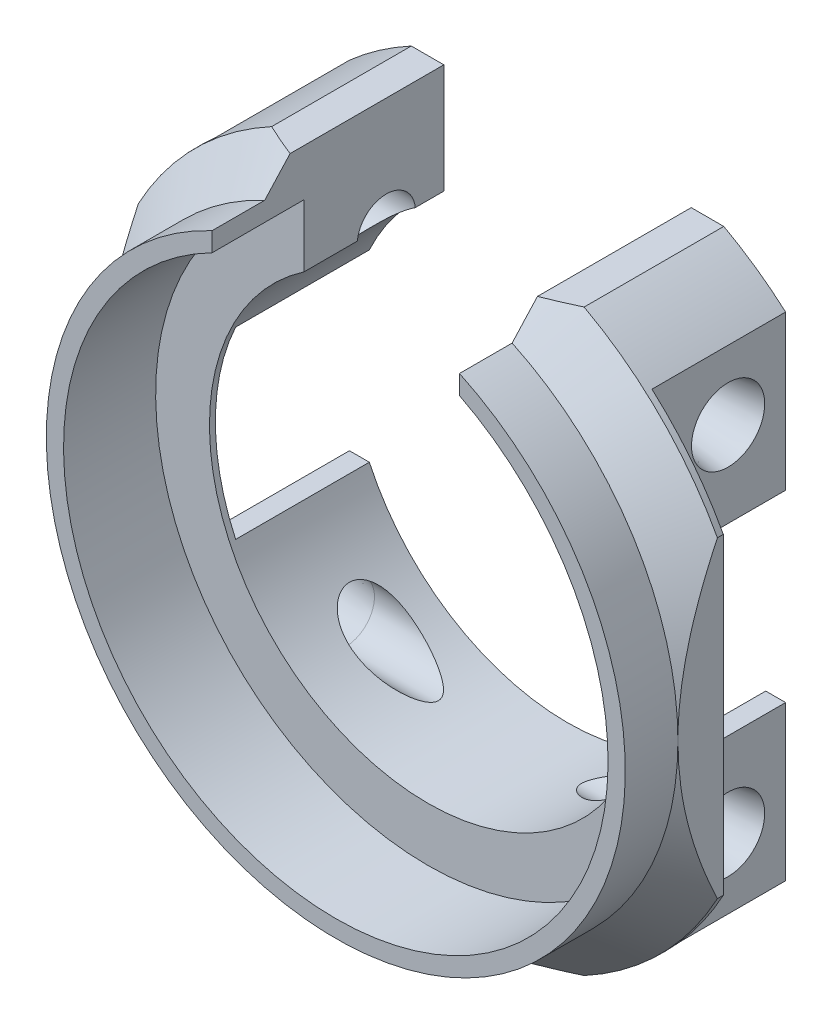
SolidWorks part; units mm, degrees
material "6061-T6 (SS)"
ref_plane "Front Plane" through (0, 0, 0) normal (0, 0, 1) x (1, 0, 0)
ref_plane "Top Plane" through (0, 0, 0) normal (0, 1, 0) x (1, 0, 0)
ref_plane "Right Plane" through (0, 0, 0) normal (1, 0, 0) x (0, 0, -1)
sketch "Sketch1" plane through (0, 0, 0) normal (0, 0, 1) x (1, 0, 0)
  line L1 (-16.637, -17.145) -> (16.637, -17.145) construction
  line L2 (-16.637, -17.145) -> (-16.637, 17.145) construction
  line L3 (-16.637, 17.145) -> (16.637, 17.145) construction
  line L4 (16.637, -17.145) -> (16.637, 17.145) construction
  line L5 (0, 17.145) -> (0, -17.145) construction
  line L6 (-16.637, 0) -> (16.637, 0) construction
  line L7 (-22, -22) -> (22, -22)
  line L8 (-22, -22) -> (-22, 22)
  line L9 (-22, 22) -> (22, 22)
  line L10 (22, -22) -> (22, 22)
  line L11 (0, 22) -> (0, -22) construction
  line L12 (-22, 0) -> (22, 0) construction
  circle A0 centre (0, 0) radius 16.002 construction
  circle A1 centre (0, 0) radius 16.602
  point P0 (0, 0)
  dimension "D3" = 32.004
  dimension "D1" = 33.274
  dimension "D2" = 34.29
  dimension "D4" = 44
  dimension "D6" = 0.6
extrude "Boss-Extrude1" add sketch "Sketch1" along normal blind 0.45
sketch "Sketch2" plane through (0, 0, 0) normal (0, 0, -1) x (-1, 0, 0)
  line L0 (-22, 22) -> (22, 22) construction
  line L1 (-16.5735, -22) -> (16.5735, -22)
  line L2 (-16.5735, -22) -> (-16.5735, 22)
  line L3 (-16.5735, 22) -> (16.5735, 22)
  line L4 (16.5735, -22) -> (16.5735, 22)
  line L5 (0, 22) -> (0, -22) construction
  line L6 (-16.5735, 0) -> (16.5735, 0) construction
  line L7 (15.0611, 6.985) -> (16.5735, 6.985)
  line L9 (15.0611, -6.985) -> (16.5735, -6.985)
  line L11 (-15.0611, -6.985) -> (-16.5735, -6.985)
  line L12 (-15.0611, 6.985) -> (-16.5735, 6.985)
  circle A0 centre (0, 0) radius 16.602 construction
  circle A1 centre (0, 0) radius 16.602
  point P0 (0, 0)
  circle M15 centre (0, 0) radius 16.602
  dimension "D1" = 33.147
  dimension "D2" = 6.985
extrude "Boss-Extrude2" add sketch "Sketch2" along normal blind 10.16 contours L7 L4 L3 M15 | L9 L1 L4 M15 region at (0, -17.0395, 0) region at (0, 17.0395, 0)
sketch "Sketch3" plane through (-16.5735, 0, 0) normal (-1, 0, 0) x (0, 0, 1)
  line L0 (0, 6.985) -> (0, 22) construction
  circle A0 centre (-5.788, 13.4747) radius 2.7813
  circle A1 centre (-5.788, -13.4747) radius 2.7813
  dimension "D3" = 5.5626
  dimension "D1" = 26.9494
  dimension "D2" = 13.4747
  dimension "D4" = 5.788
extrude "Cut-Extrude1" cut sketch "Sketch3" against normal blind 4.064 draft 8
mirror "Mirror1" about plane through (0, 0, 0) normal (1, 0, 0) of "Cut-Extrude1"
sketch "Sketch4" plane through (-12.5095, 0, 0) normal (-1, 0, 0) x (0, 0, 1)
  circle A0 centre (-5.788, -13.4747) radius 2.2101 construction
  circle A1 centre (-5.788, 13.4747) radius 2.2101 construction
  circle A2 centre (-5.788, -13.4747) radius 2.2101
  circle A3 centre (-5.788, 13.4747) radius 2.2101
extrude "Cut-Extrude2" cut sketch "Sketch4" against normal through all
sketch "Sketch5" plane through (0, 0, 0.45) normal (0, 0, 1) x (1, 0, 0)
  circle A0 centre (0, 0) radius 18.4912 construction
  dimension "D1" = 36.9824
sketch "Sketch6" plane through (0, 0, 0.45) normal (0, 0, 1) x (1, 0, 0)
  line L0 (-22, 22) -> (-22, -22) construction
  line L1 (-25, -25) -> (25, -25)
  line L2 (-25, -25) -> (-25, 25)
  line L3 (-25, 25) -> (25, 25)
  line L4 (25, -25) -> (25, 25)
  line L5 (0, 25) -> (0, -25) construction
  line L6 (-25, 0) -> (25, 0) construction
  line L8 (-22, -22) -> (22, -22) construction
  point P0 (0, 0)
  dimension "D1" = 3
  dimension "D2" = 3
chamfer "Chamfer2" distance 2 angle 45 1 edges at (0, -22, -10.16)
sketch "Sketch12" plane through (0, 0, 0.45) normal (0, 0, 1) x (1, 0, 0)
  line L0 (0, 25) -> (0, -25) construction
  circle A0 centre (0, 0) radius 20.291 construction
  circle A1 centre (0, 0) radius 22
  circle A2 centre (0, 0) radius 20.691
  dimension "D1" = 40.582
  dimension "D2" = 44
  dimension "D3" = 0.4
extrude "Boss-Extrude4" add sketch "Sketch12" along normal blind 7
sketch "Sketch13" plane through (0, 0, 0.45) normal (0, 0, 1) x (1, 0, 0)
  circle A0 centre (0, 0) radius 25
  circle A1 centre (0, 0) radius 53.181
  circle A2 centre (0, 0) radius 22 construction
  dimension "D1" = 3
extrude "Cut-Extrude9" cut sketch "Sketch13" against normal through all
chamfer "Chamfer3" distance 3 angle 45 4 edges at (15.5563, 15.5563, 0.45) (-15.5563, 15.5563, 0.45) (-15.5563, -15.5563, 0.45) (15.5563, -15.5563, 0.45)
sketch "Sketch14" plane through (0, 0, 7.45) normal (0, 0, 1) x (1, 0, 0)
  line L0 (0, 22) -> (-11.8743, 22) construction
  line L1 (-9.4, 22) -> (9.4, 22)
  line L2 (-9.4, 22) -> (-9.4, 13.6845)
  line L3 (-9.4, 13.6845) -> (9.4, 13.6845)
  line L4 (9.4, 22) -> (9.4, 13.6845)
  line L5 (0, 25) -> (0, -25) construction
  circle A0 centre (0, 0) radius 16.602 construction
  dimension "D1" = 18.8
  dimension "D2" = 9.4
extrude "Cut-Extrude10" cut sketch "Sketch14" against normal through all
